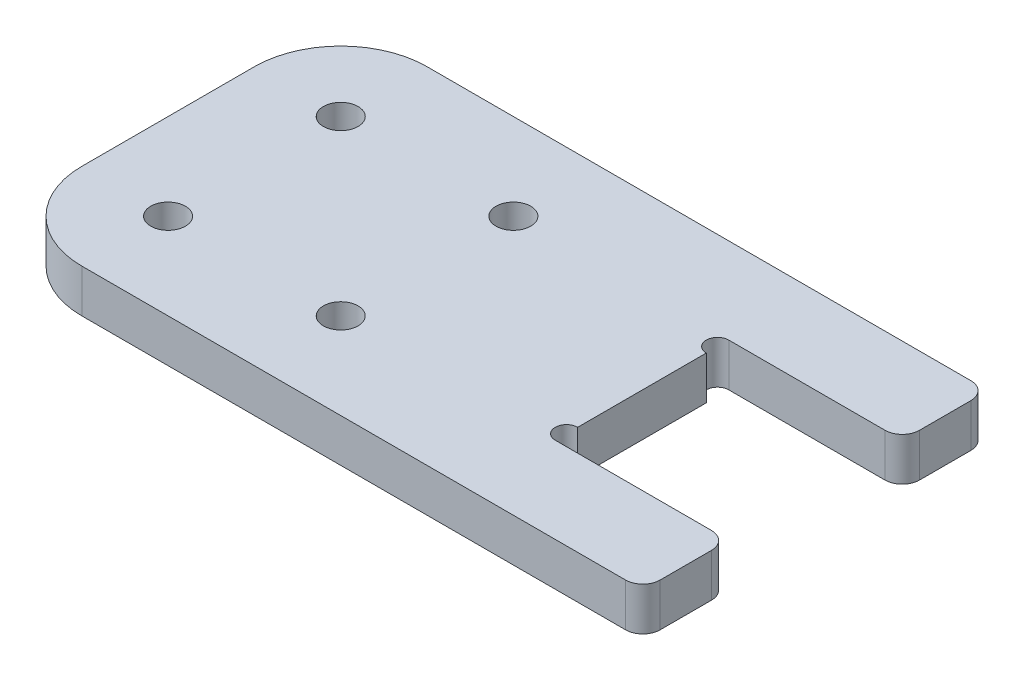
SolidWorks part; units mm, degrees
material "6061-T6 (SS)"
ref_plane "Front Plane" through (0, 0, 0) normal (0, 0, 1) x (1, 0, 0)
ref_plane "Top Plane" through (0, 0, 0) normal (0, 1, 0) x (1, 0, 0)
ref_plane "Right Plane" through (0, 0, 0) normal (1, 0, 0) x (0, 0, -1)
sketch "Sketch1" plane through (0, 0, 0) normal (0, 1, 0) x (1, 0, 0)
  line L0 (34.925, 25.4) -> (60.325, 25.4)
  line L1 (-34.925, -25.4) -> (34.925, -25.4)
  line L2 (-34.925, -25.4) -> (-34.925, 25.4)
  line L3 (-34.925, 25.4) -> (34.925, 25.4)
  line L5 (-34.925, -25.4) -> (34.925, 25.4) construction
  line L6 (-34.925, 25.4) -> (34.925, -25.4) construction
  line L7 (60.325, 25.4) -> (60.325, -25.4)
  line L8 (60.325, -25.4) -> (34.925, -25.4)
  point P0 (0, 0)
  dimension "D1" = 69.85
  dimension "D2" = 50.8
  dimension "D3" = 25.4
extrude "Boss-Extrude1" add sketch "Sketch1" along normal blind 6.35
sketch "Sketch2" plane through (0, 6.35, 0) normal (0, 1, 0) x (1, 0, 0)
  line L4 (60.325, 25.4) -> (-34.925, 25.4) construction
  line L5 (-34.925, -25.4) -> (60.325, -25.4) construction
  line L7 (15.875, 25.4) -> (15.875, -25.4) construction
  line L8 (-34.925, 25.4) -> (-34.925, -25.4) construction
  dimension "D1" = 50.8
hole_wizard "#10 Clearance Hole1" positions "Sketch3" profile "Sketch4" hole size "#10" standard "ANSI Inch" end condition through all
sketch "Sketch3" plane through (0, 6.35, 0) normal (0, 1, 0) x (1, 0, 0)
  line L4 (-22.225, 25.4) -> (-22.225, -25.4) construction
  line L5 (60.325, 25.4) -> (-34.925, 25.4) construction
  line L6 (-34.925, -25.4) -> (60.325, -25.4) construction
  line L8 (3.175, 25.4) -> (3.175, -25.4) construction
  line L9 (-34.925, 25.4) -> (-34.925, -25.4) construction
  line L11 (-34.925, 12.7) -> (15.875, 12.7) construction
  line L13 (-34.925, -12.7) -> (15.875, -12.7) construction
  point P0 (-22.225, 12.7)
  point P2 (3.175, 12.7)
  point P4 (3.175, -12.7)
  point P6 (-22.225, -12.7)
  dimension "D1" = 12.7
  dimension "D2" = 38.1
  dimension "D3" = 12.7
  dimension "D4" = 12.7
  dimension "D5" = 50.8
  dimension "D6" = 50.8
sketch "Sketch4" plane through (-22.225, 6.35, -12.7) normal (1, 0, 0) x (0, 0, 1)
  line L0 (0, 0) -> (0, 6.35)
  line L1 (0, 6.35) -> (2.5527, 6.35)
  line L2 (2.5527, 6.35) -> (2.5527, 0)
  line L5 (2.5527, 0) -> (0, 0)
  line L11 (0, -6.35) -> (0, 107.95) construction
  dimension "Thru Hole Dia." = 5.1054
  dimension "Thru Hole Depth" = 6.35
sketch "Sketch5" plane through (0, 6.35, 0) normal (0, 1, 0) x (1, 0, 0)
  line L1 (60.325, -25.4) -> (60.325, 25.4) construction
  line L2 (34.798, -12.7635) -> (60.325, -12.7635)
  line L4 (34.798, -12.7635) -> (34.798, 12.7635)
  line L5 (34.798, 12.7635) -> (60.325, 12.7635)
  line L6 (60.325, -12.7635) -> (60.325, 12.7635)
  line L7 (34.798, -12.7635) -> (60.325, 12.7635) construction
  line L8 (34.798, 12.7635) -> (60.325, -12.7635) construction
  line L13 (60.325, 12.7635) -> (60.325, 25.4) construction
  line L14 (60.325, -12.7635) -> (60.325, -25.4) construction
  dimension "D3" = 25.527
extrude "Cut-Extrude1" cut sketch "Sketch5" against normal through all
sketch "Sketch6" plane through (0, 6.35, 0) normal (0, 1, 0) x (1, 0, 0)
  line L0 (34.798, 12.7635) -> (34.798, -12.7635) construction
  line L1 (34.798, 9.4615) -> (34.798, 12.7635)
  line L2 (34.798, 0) -> (41.7316, 0) construction
  line L3 (34.798, -9.4615) -> (34.798, -12.7635)
  arc A0 (34.798, 12.7635) -> (34.798, 9.4615) centre (34.798, 11.1125) ccw
  arc A1 (34.798, -12.7635) -> (34.798, -9.4615) centre (34.798, -11.1125) cw
  dimension "D1" = 3.302
extrude "Cut-Extrude2" cut sketch "Sketch6" against normal through all
fillet "Fillet1" radius 2.54 4 edges at (60.325, 3.175, 12.7635) (60.325, 3.175, -12.7635) (60.325, 3.175, -25.4) (60.325, 3.175, 25.4)
fillet "Fillet2" radius 12.7 2 edges at (-34.925, 3.175, -25.4) (-34.925, 3.175, 25.4)
